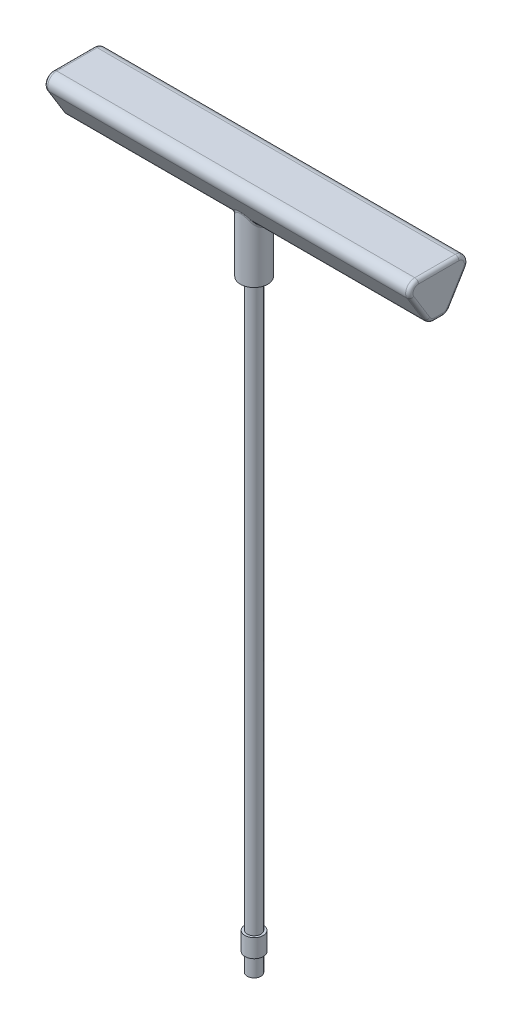
SolidWorks part; units mm, degrees
ref_plane "Front Plane" through (0, 0, 0) normal (0, 0, 1) x (1, 0, 0)
ref_plane "Top Plane" through (0, 0, 0) normal (0, 1, 0) x (1, 0, 0)
ref_plane "Right Plane" through (0, 0, 0) normal (1, 0, 0) x (0, 0, -1)
sketch "Sketch3" plane through (0, 0, 0) normal (1, 0, 0) x (0, 0, -1)
  line L0 (0, 0) -> (50.8, 0)
  line L1 (50.8, 0) -> (31.75, -31.0258)
  line L2 (31.75, -31.0258) -> (19.05, -31.0258)
  line L3 (19.05, -31.0258) -> (0, 0)
  dimension "D1" = 50.8
  dimension "D2" = 12.7
  dimension "D3" = 19.05
  dimension "D4" = 31.0258
extrude "Boss-Extrude1" add sketch "Sketch3" along normal blind 254
fillet "Fillet1" radius 6.35 4 edges at (127, 0, -50.8) (127, -31.0258, -31.75) (127, -31.0258, -19.05) (127, 0, 0)
fillet "Fillet2" radius 2.54 16 edges at (0, -3.2497, -44.9913) (0, -18.8355, -39.2349) (0, -30.2175, -31.2978) (0, -31.0258, -25.4) (0, -30.2175, -19.5022) (0, -18.8355, -11.5651) (0, -3.2497, -5.8087) (254, -3.2497, -44.9913) (254, -18.8355, -39.2349) (254, -30.2175, -31.2978) (254, -31.0258, -25.4) (254, -30.2175, -19.5022) (254, -18.8355, -11.5651) (254, -3.2497, -5.8087) (0, 0, -25.4) (254, 0, -25.4)
sketch "Sketch4" plane through (0, -31.0258, 0) normal (0, -1, 0) x (1, 0, 0)
  line L1 (251.46, -22.6025) -> (2.54, -22.6025) construction
  line L2 (2.54, -28.1975) -> (251.46, -28.1975) construction
  circle A0 centre (125.6715, -25.3965) radius 9.525
  dimension "D3" = 19.05
  dimension "D1" = 5.595
  dimension "D2" = 2.794
extrude "Boss-Extrude2" add sketch "Sketch4" against normal up to next (31.0258 mm away) and the other way blind 38.1
sketch "Sketch5" plane through (0, -69.1258, 0) normal (0, -1, 0) x (1, 0, 0)
  circle A0 centre (125.6715, -25.3965) radius 4.7625
  dimension "D1" = 9.525
extrude "Boss-Extrude3" add sketch "Sketch5" along normal blind 419.1
ref_plane "Plane1" through (0, -462.8258, 0) normal (0, -1, 0) x (-1, 0, 0)
sketch "Sketch9" plane through (0, -462.8258, 0) normal (0, -1, 0) x (-1, 0, 0)
  circle A0 centre (-125.6715, 25.3965) radius 6.35
  dimension "D1" = 12.7
extrude "Boss-Extrude5" add sketch "Sketch9" along normal blind 12.7
fillet "Fillet5" radius 2.54 8 edges at (132.6045, -29.8095, -18.8651) (135.1965, -31.0258, -25.4002) (135.1045, -18.5008, -26.7171) (125.6715, -25.8605, -34.9215) (118.7778, -29.7842, -31.9693) (116.1465, -31.0258, -25.4002) (116.2335, -18.5078, -24.1119) (125.6715, -25.8492, -15.8715)
